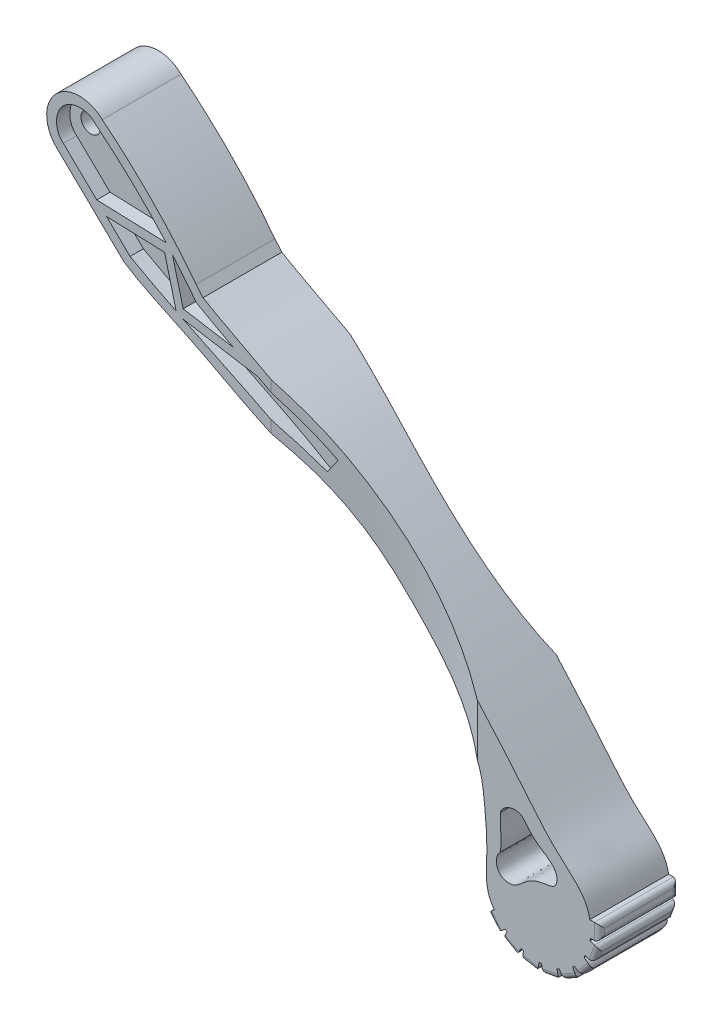
SolidWorks part; units mm, degrees
ref_plane "Front Plane" through (0, 0, 0) normal (0, 0, 1) x (1, 0, 0)
ref_plane "Top Plane" through (0, 0, 0) normal (0, 1, 0) x (1, 0, 0)
ref_plane "Right Plane" through (0, 0, 0) normal (1, 0, 0) x (0, 0, -1)
sketch "Sketch1" plane through (0, 0, 0) normal (0, 0, 1) x (1, 0, 0)
  line L0 (-410.6585, 121.2034) -> (374.6748, 121.2034) construction
  line L1 (26.5559, -34.5498) -> (-8.228, -0.9018)
  arc A0 (15.2735, 23.3931) -> (-8.228, -0.9018) centre (3.5227, 11.2456) ccw
  arc A1 (218.53, -229.4896) -> (266.6412, -208.28) centre (240.0605, -213.1568) ccw
  spline S0 degree 2 poles (63.6799, -25.8784) (42.4869, 1.5768) (15.2735, 23.3931) knots 0 0 0 1 1 1
  spline S1 degree 3 poles (26.5559, -34.5498) (38.327, -42.0251) (60.507, -51.1102) (90.5082, -68.1186) (121.4072, -81.3077) (149.5206, -102.7069) (173.3953, -128.5865) (195.7007, -147.031) (210.256, -165.322) (212.5963, -185.1607) (214.4663, -205.7021) (212.0357, -222.8476) (218.53, -229.4896) knots 0 0 0 0 0.142543 0.244853 0.353362 0.485795 0.603192 0.71314 0.784774 0.833635 0.913763 1 1 1 1
  spline S2 degree 1 poles (63.6799, -25.8784) (67.1861, -30.0955) knots 0 0 1 1
  spline S3 degree 3 poles (67.1861, -30.0955) (85.8924, -40.9613) (114.1343, -53.4624) (171.4796, -98.2429) (212.6551, -141.5391) (249.7544, -188.0143) (265.1455, -198.3464) (266.6412, -208.28) knots 0 0 0 0 0.240888 0.338157 0.805261 0.897011 1 1 1 1
  spline S4 degree 3 poles (227.2011, -179.6058) (232.1806, -176.7124) (239.6892, -183.0079) (245.2311, -192.2789) (253.7114, -195.3444) (254.4334, -204.5189) (247.0532, -206.1992) (241.0074, -202.0632) (233.627, -206.0397) (229.0588, -213.8571) (220.0328, -208.8902) (221.8903, -205.413) knots 0 0 0 0 0.194203 0.319739 0.427614 0.518169 0.584349 0.673943 0.785664 0.86586 1 1 1 1
  spline S5 degree 3 poles (221.8903, -205.413) (222.606, -199.9471) (220.1629, -191.2642) (222.6164, -180.7611) (227.2011, -179.6058) knots 0 0 0 0 0.563485 1 1 1 1
extrude "Boss-Extrude2" add sketch "Sketch1" along normal blind 20.32 and the other way blind 20.32 contours S0 A0 L1 S1 A1 S3 S2
sketch "Sketch3" plane through (0, 0, 0) normal (0, 0, 1) x (1, 0, 0)
  line L0 (138.1586, -72.3364) -> (128.1606, -87.2769) construction
  line L1 (-410.605, 120.6628) -> (374.7283, 120.6628) construction
  line L2 (-8.228, -0.9018) -> (26.5559, -34.5498) construction
  line L3 (-4.8078, 2.8575) -> (29.6246, -30.4504)
  line L4 (131.3387, -73.3934) -> (126.6496, -80.4006)
  arc A0 (15.2735, 23.3931) -> (-8.228, -0.9018) centre (3.5227, 11.2456) ccw construction
  parabola Q0 (63.6799, -25.8784) -> (15.2735, 23.3931) focus (-59.7172, -103.5969) apex (45.7538, -4.8076) construction
  spline S0 degree 3 poles (67.1861, -30.0955) (85.8924, -40.9613) (114.1343, -53.4624) (171.4796, -98.2429) (212.6551, -141.5391) (249.7544, -188.0143) (265.1455, -198.3464) (266.6412, -208.28) knots 0 0 0 0 0.240888 0.338157 0.805261 0.897011 1 1 1 1 construction
  spline S1 degree 3 poles (26.5559, -34.5498) (38.327, -42.0251) (60.507, -51.1102) (90.5082, -68.1186) (121.4072, -81.3077) (149.5206, -102.7069) (173.3953, -128.5865) (195.7007, -147.031) (210.256, -165.322) (212.5963, -185.1607) (214.4663, -205.7021) (212.0357, -222.8476) (218.53, -229.4896) knots 0 0 0 0 0.142543 0.244853 0.353362 0.485795 0.603192 0.71314 0.784774 0.833635 0.913763 1 1 1 1 construction
  spline S2 degree 3 poles (138.1586, -72.3364) (116.7595, -54.6964) (91.0219, -43.8151) (67.1861, -30.0955) knots 0 0 0 0 1 1 1 1 construction
  spline S3 degree 3 poles (128.1606, -87.2769) (95.7087, -67.0919) (59.7325, -53.4252) (26.5559, -34.5498) knots 0 0 0 0 1 1 1 1 construction
  spline S4 degree 2 poles (67.1861, -30.0955) (44.4752, -0.311) (15.2735, 23.3931) knots 0 0 0 1 1 1 construction
  spline S5 degree 3 poles (-8.228, -0.9018) (-15.3538, 5.1935) (-14.0741, 28.2467) (9.0031, 30.2984) (15.2735, 23.3931) knots 0 0 0 0 0.5 1 1 1 1 construction
  spline S6 degree 1 poles (63.7662, -33.9884) (11.7721, 19.6922) knots 0 0 1 1 construction
  spline S7 degree 1 poles (-4.8078, 2.8575) (11.7721, 19.6922) knots 0 0 1 1 construction
  spline S8 degree 1 poles (126.6496, -80.4006) (29.6246, -30.4504) knots 0 0 1 1 construction
  spline S9 degree 1 poles (131.3387, -73.3934) (63.7662, -33.9884) knots 0 0 1 1 construction
  spline S10 degree 2 poles (63.7662, -33.9884) (62.6899, -32.5708) (60.5375, -29.7942) (57.2604, -25.665) (50.5342, -17.5735) (30.0945, 4.8551) (11.7721, 19.6922) knots -0.013643 -0.013643 -0.013643 0.034112 0.081867 0.177377 0.368398 1.005132 1.005132 1.005132
  spline S11 degree 3 poles (11.7721, 19.6922) (11.6777, 19.7963) (11.5068, 19.9855) (11.3956, 20.1049) (11.2623, 20.2441) (11.1, 20.4053) (10.8308, 20.6571) (10.4848, 20.9514) (9.9074, 21.3849) (9.1419, 21.8576) (7.8239, 22.4735) (6.0088, 22.9797) (3.6408, 23.1437) (1.2122, 22.8511) (-1.1281, 22.1213) (-3.2426, 20.9945) (-4.9876, 19.5649) (-6.3764, 17.8096) (-7.8189, 14.9821) (-8.4498, 11.7104) (-8.1648, 8.5553) (-7.5101, 6.3768) (-6.619, 4.7869) (-5.8028, 3.7971) (-5.3474, 3.3372) (-5.099, 3.1094) (-4.9808, 3.0055) (-4.8968, 2.9336) (-4.8359, 2.8815) (-4.8078, 2.8575) knots -0.002763 -0.002763 -0.002763 -0.002763 0.005125 0.009069 0.013013 0.020901 0.028789 0.044565 0.060341 0.091893 0.123445 0.186549 0.249652 0.312756 0.37586 0.438964 0.502068 0.565171 0.628275 0.754483 0.817587 0.880691 0.943794 0.975346 0.991122 0.99901 1.002954 1.004926 1.006898 1.006898 1.006898 1.006898
  spline S12 degree 3 poles (29.6246, -30.4504) (33.5297, -32.6631) (41.4097, -36.9406) (57.4778, -45.1196) (77.9327, -54.897) (98.4763, -64.8746) (114.6905, -73.45) (122.7011, -78.03) (126.6496, -80.4006) knots 0.042191 0.042191 0.042191 0.042191 0.161209 0.280227 0.518262 0.756297 0.875315 0.994333 0.994333 0.994333 0.994333
  spline S13 degree 3 poles (131.3387, -73.3934) (126.2721, -69.4796) (115.6861, -62.3274) (98.7258, -52.7567) (84.1423, -45.155) (73.9087, -39.6826) (68.821, -36.8679) (65.9156, -35.2259) (64.4839, -34.4015) (63.7662, -33.9884) knots 0.057213 0.057213 0.057213 0.057213 0.296006 0.5348 0.773593 0.89299 0.952688 0.982538 1.012387 1.012387 1.012387 1.012387
sketch "Sketch7" plane through (0, 0, 20.32) normal (0, 0, 1) x (1, 0, 0)
  line L0 (138.1586, -72.3364) -> (128.1606, -87.2769) construction
  line L1 (-8.228, -0.9018) -> (26.5559, -34.5498) construction
  line L2 (131.3387, -73.3934) -> (126.6496, -80.4006)
  line L3 (-4.8078, 2.8575) -> (29.6246, -30.4504)
  spline S0 degree 3 poles (128.1606, -87.2769) (95.7087, -67.0919) (59.7325, -53.4252) (26.5559, -34.5498) knots 0 0 0 0 1 1 1 1 construction
  spline S1 degree 3 poles (138.1586, -72.3364) (116.7595, -54.6964) (91.0219, -43.8151) (67.1861, -30.0955) knots 0 0 0 0 1 1 1 1 construction
  spline S2 degree 2 poles (67.1861, -30.0955) (44.4752, -0.311) (15.2735, 23.3931) knots 0 0 0 1 1 1 construction
  spline S3 degree 3 poles (-8.228, -0.9018) (-15.3538, 5.1935) (-14.0741, 28.2467) (9.0031, 30.2984) (15.2735, 23.3931) knots 0 0 0 0 0.5 1 1 1 1 construction
  spline S4 degree 1 poles (-4.8078, 2.8575) (11.7721, 19.6922) knots 0 0 1 1 construction
  spline S5 degree 1 poles (63.7662, -33.9884) (11.7721, 19.6922) knots 0 0 1 1 construction
  spline S6 degree 1 poles (131.3387, -73.3934) (63.7662, -33.9884) knots 0 0 1 1 construction
  spline S7 degree 1 poles (126.6496, -80.4006) (29.6246, -30.4504) knots 0 0 1 1 construction
  spline S8 degree 3 poles (-4.8078, 2.8575) (-4.8359, 2.8815) (-4.8968, 2.9336) (-4.9808, 3.0055) (-5.099, 3.1094) (-5.3474, 3.3372) (-5.8028, 3.7971) (-6.619, 4.7869) (-7.5101, 6.3768) (-8.1648, 8.5553) (-8.4498, 11.7104) (-7.8189, 14.9821) (-6.3764, 17.8096) (-4.9876, 19.5649) (-3.2426, 20.9945) (-1.1281, 22.1213) (1.2122, 22.8511) (3.6408, 23.1437) (6.0088, 22.9797) (7.8239, 22.4735) (9.1419, 21.8576) (9.9074, 21.3849) (10.4848, 20.9514) (10.8308, 20.6571) (11.1, 20.4053) (11.2623, 20.2441) (11.3956, 20.1049) (11.5068, 19.9855) (11.6777, 19.7963) (11.7721, 19.6922) knots -0.002763 -0.002763 -0.002763 -0.002763 -0.000791 0.001181 0.005125 0.013013 0.028789 0.060341 0.123445 0.186549 0.249652 0.37586 0.438964 0.502068 0.565171 0.628275 0.691379 0.754483 0.817587 0.880691 0.912243 0.943794 0.95957 0.975346 0.983234 0.991122 0.995066 0.99901 1.006898 1.006898 1.006898 1.006898
  spline S9 degree 2 poles (11.7721, 19.6922) (30.0945, 4.8551) (50.5342, -17.5735) (57.2604, -25.665) (60.5375, -29.7942) (62.6899, -32.5708) (63.7662, -33.9884) knots -0.013643 -0.013643 -0.013643 0.623092 0.814112 0.909622 0.957377 1.005132 1.005132 1.005132
  spline S10 degree 3 poles (63.7662, -33.9884) (64.4839, -34.4015) (65.9156, -35.2259) (68.821, -36.8679) (73.9087, -39.6826) (84.1423, -45.155) (98.7258, -52.7567) (115.6861, -62.3274) (126.2721, -69.4796) (131.3387, -73.3934) knots 0.057213 0.057213 0.057213 0.057213 0.087062 0.116911 0.17661 0.296006 0.5348 0.773593 1.012387 1.012387 1.012387 1.012387
  spline S11 degree 3 poles (126.6496, -80.4006) (122.7011, -78.03) (114.6905, -73.45) (98.4763, -64.8746) (77.9327, -54.897) (57.4778, -45.1196) (41.4097, -36.9406) (33.5297, -32.6631) (29.6246, -30.4504) knots 0.042191 0.042191 0.042191 0.042191 0.161209 0.280227 0.518262 0.756297 0.875315 0.994333 0.994333 0.994333 0.994333
extrude "Cut-Extrude5" cut sketch "Sketch7" against normal blind 6.858
mirror "Mirror1" about plane through (0, 0, 0) normal (0, 0, 1) of "Cut-Extrude5"
sketch "Sketch10" plane through (0, 0, 0) normal (0, 0, 1) x (1, 0, 0)
  line L0 (15.2735, 23.3931) -> (-10.2875, 1.2752)
  line L1 (-4.8078, 2.8575) -> (29.6246, -30.4504) construction
  line L2 (12.4084, -13.7965) -> (50.5351, -15.1415)
  line L3 (50.5351, -15.1415) -> (56.9596, -40.1516)
  line L4 (56.9596, -40.1516) -> (82.89, -44.4634)
  line L5 (53.6974, -44.2394) -> (47.3971, -19.7128)
  line L6 (53.6974, -44.2394) -> (95.6324, -51.2126)
  line L7 (47.3971, -19.7128) -> (17.4317, -18.6557)
  line L8 (82.89, -44.4634) -> (83.6362, -43.1576)
  line L9 (95.6324, -51.2126) -> (96.1493, -50.3081)
  line L10 (96.1493, -50.3081) -> (83.6362, -43.1576)
  line L11 (12.4084, -13.7965) -> (11.461, -14.7758)
  line L12 (17.4317, -18.6557) -> (16.4898, -19.6294)
  line L13 (16.4898, -19.6294) -> (11.461, -14.7758)
  circle A1 centre (2.493, 12.3341) radius 5.08
  spline S0 degree 3 poles (-8.228, -0.9018) (-15.3538, 5.1935) (-14.0741, 28.2467) (9.0031, 30.2984) (15.2735, 23.3931) knots 0 0 0 0 0.5 1 1 1 1 construction
  spline S2 degree 3 poles (131.3387, -73.3934) (126.2721, -69.4796) (115.6861, -62.3274) (98.7258, -52.7567) (84.1423, -45.155) (73.9087, -39.6826) (68.821, -36.8679) (65.9156, -35.2259) (64.4839, -34.4015) (63.7662, -33.9884) knots 0.057213 0.057213 0.057213 0.057213 0.296006 0.5348 0.773593 0.89299 0.952688 0.982538 1.012387 1.012387 1.012387 1.012387 construction
extrude "Boss-Extrude4" add sketch "Sketch10" along normal up to surface (20.32 mm away) contours L3 L4 L8 L10 L9 L6 L5 L7 L12 L13 L11 L2 | A1 up to face at (62.984, -34.8056, 20.32)
mirror "Mirror3" about plane through (0, 0, 0) normal (0, 0, 1) of bodies 109
sketch "Sketch11" plane through (0, 0, 0) normal (0, 1, 0) x (1, 0, 0)
  line L0 (67.1861, 20.32) -> (266.6412, 20.32)
  line L1 (266.6412, 20.32) -> (266.6412, -20.32)
  line L2 (266.6412, -20.32) -> (67.1861, -20.32)
  line L3 (67.1861, -20.32) -> (67.1861, 20.32)
  line L4 (102.3796, -20.32) -> (208.6255, -20.32)
  line L5 (-485.65, 0) -> (485.65, 0) construction
  line L6 (102.3796, 20.32) -> (208.6255, 20.32)
  spline S0 degree 3 poles (102.3796, -20.32) (135.9132, -13.6193) (176.2265, -4.5731) (208.6255, -20.32) knots 0 0 0 0 1 1 1 1
  spline S1 degree 3 poles (102.3796, 20.32) (135.9132, 13.6193) (176.2265, 4.5731) (208.6255, 20.32) knots 0 0 0 0 1 1 1 1
extrude "Cut-Extrude9" cut sketch "Sketch11" against normal blind 621.03 contours S0 L2 | L0 S1 region at (159.9441, 0, -16.8578) region at (159.9441, 0, 16.8578)
sketch "Sketch12" plane through (0, 0, 0) normal (0, 0, 1) x (1, 0, 0)
  spline S0 degree 3 poles (220.5132, -183.3018) (221.5431, -179.4366) (230.1634, -176.0109) (235.049, -183.6277) (239.6129, -187.8562) (245.3318, -191.2909) (250.334, -195.773) (249.2622, -203.0491) (242.2874, -203.6447) (236.4248, -205.2693) (231.6951, -209.1254) (227.4743, -213.1898) (217.7706, -212.1725) (217.7802, -203.3131) (220.5132, -200.954) knots 0 0 0 0 0.140789 0.21554 0.293169 0.361812 0.454084 0.50975 0.573954 0.668559 0.729438 0.786275 0.872193 1 1 1 1
  spline S1 degree 3 poles (220.5132, -200.954) (221.3884, -195.0713) (220.2113, -189.1946) (220.5132, -183.3018) knots 0 0 0 0 1 1 1 1
extrude "Cut-Extrude10" cut sketch "Sketch12" against normal blind 621.03 and the other way blind 621.03
sketch "Sketch13" plane through (0, 0, 20.32) normal (0, 0, 1) x (1, 0, 0)
  line L0 (265.8448, -208.088) -> (271.5285, -208.088)
  line L1 (271.5285, -208.088) -> (271.5285, -216.1724)
  line L2 (271.5285, -216.1724) -> (266.0514, -216.1724)
  line L3 (265.8448, -208.088) -> (262.556, -212.3652)
  line L4 (262.556, -212.3652) -> (266.0514, -216.1724)
extrude "Boss-Extrude10" add sketch "Sketch13" against normal up to surface (40.64 mm away) contours L4 L2 L1 L0 L3 up to face at (219.2096, -173.7621, -20.32)
pattern_circular "CirPattern2" count 8 every 20 about axis through (240.0605, -213.1568, -20.32) along (0, 0, 1) of "Boss-Extrude10" reverse direction yes
fillet "Fillet2" radius 2.54 32 edges at (271.5285, -212.1302, -20.32) (271.5285, -216.1724, 0) (271.5285, -208.088, 0) (271.5285, -212.1302, 20.32) (269.9819, -222.9548, -20.32) (268.5994, -226.7533, 0) (271.3644, -219.1564, 0) (269.9819, -222.9548, 20.32) (264.8263, -232.5977, -20.32) (262.228, -235.6942, 0) (267.4246, -229.5012, 0) (264.8263, -232.5977, 20.32) (256.6835, -239.8957, -20.32) (253.1829, -241.9168, 0) (260.1842, -237.8746, 0) (256.6835, -239.8957, 20.32) (246.5358, -243.9685, -20.32) (242.555, -244.6705, 0) (250.5166, -243.2666, 0) (246.5358, -243.9685, 20.32) (235.6071, -244.3251, -20.32) (231.6263, -243.6231, 0) (239.5878, -245.027, 0) (235.6071, -244.3251, 20.32) (225.2154, -240.9222, -20.32) (221.7148, -238.9011, 0) (228.7161, -242.9433, 0) (225.2154, -240.9222, 20.32) (216.6144, -234.1705, -20.32) (214.0161, -231.074, 0) (219.2126, -237.267, 0) (216.6144, -234.1705, 20.32)
sketch "Sketch16" plane through (0, 0, 0) normal (0, 0, 1) x (1, 0, 0)
  circle A0 centre (2.493, 12.3341) radius 5.08
extrude "Cut-Extrude11" cut sketch "Sketch16" against normal blind 28.448 and the other way blind 26.162
